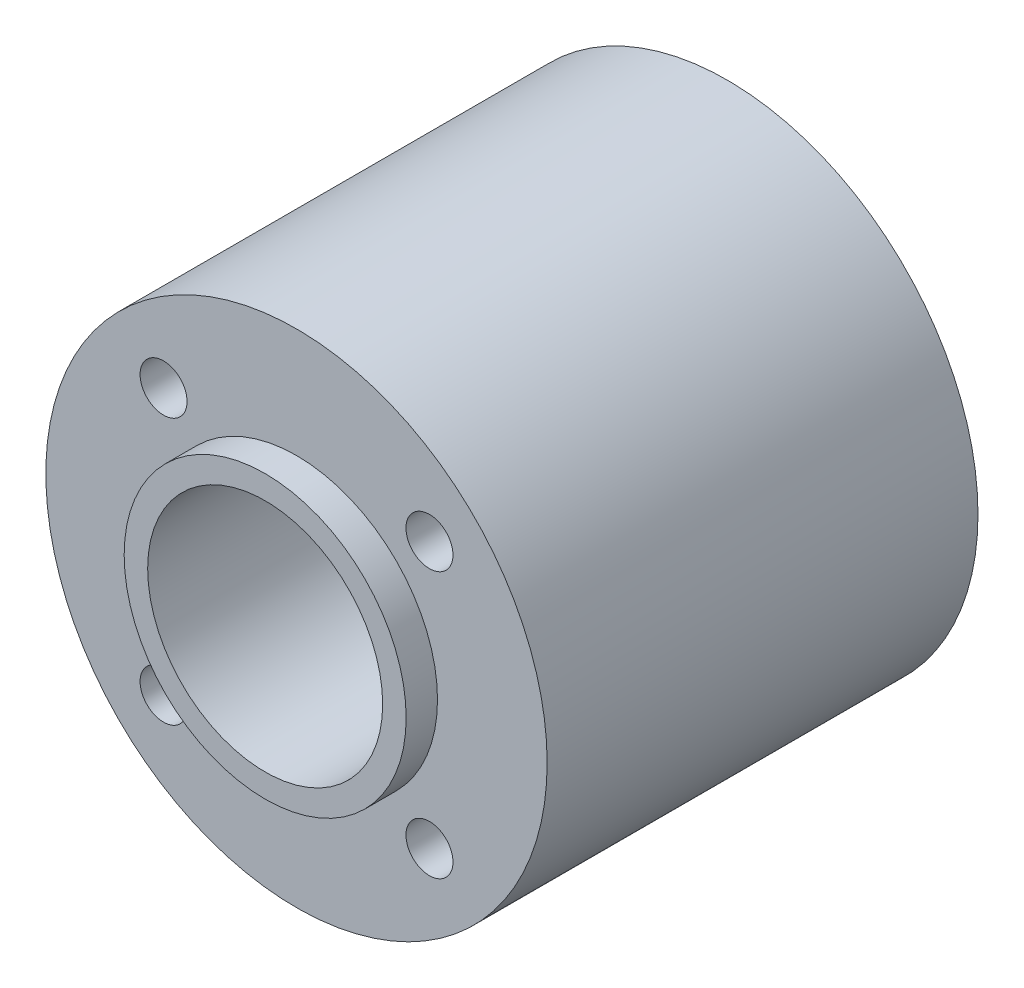
SolidWorks part; units mm, degrees
ref_plane "Front Plane" through (0, 0, 0) normal (0, 0, 1) x (1, 0, 0)
ref_plane "Top Plane" through (0, 0, 0) normal (0, 1, 0) x (1, 0, 0)
ref_plane "Right Plane" through (0, 0, 0) normal (1, 0, 0) x (0, 0, -1)
sketch "Sketch1" plane through (0, 0, 0) normal (0, 0, 1) x (1, 0, 0)
  circle A0 centre (0, 0) radius 9
  circle A1 centre (0, 0) radius 7.5
  circle A2 centre (0, 0) radius 16
  dimension "D1" = 32
  dimension "D2" = 18
  dimension "D3" = 15
extrude "Boss-Extrude1" add sketch "Sketch1" against normal blind 27.5 contours A2 A0 | A0 A1 region at (-8.7454, 0, 0) region at (-15.5475, 0, 0)
extrude "Boss-Extrude2" add sketch "Sketch1<3>" along normal blind 2 contours A0 | A1
sketch "Sketch1<3>" plane through (0, 0, 0) normal (0, 0, 1) x (1, 0, 0) same geometry as "Sketch1"
extrude "Boss-Extrude4" add sketch "Sketch1<5>" against normal blind 2 from surface contours A1 | A0 starting at face at (16, 0, -27.5)
sketch "Sketch1<5>" plane through (0, 0, 0) normal (0, 0, 1) x (1, 0, 0) same geometry as "Sketch1"
sketch "Sketch2" plane through (0, 0, 0) normal (0, 0, 1) x (1, 0, 0)
  line L0 (0, 0) -> (0, 12) construction
  line L1 (0, 12) -> (0, 0) construction
  line L2 (0, 0) -> (-8.4853, 8.4853) construction
  circle A0 centre (0, 0) radius 12 construction
  circle A1 centre (-8.4853, 8.4853) radius 1.5
  circle A2 centre (0.001, -0.001) radius 12.0014 construction
  circle A3 centre (8.4863, 8.4863) radius 1.5
  circle A4 centre (0, 0) radius 12.0014 construction
  circle A5 centre (8.4873, -8.4853) radius 1.5
  circle A6 centre (0.001, -0.001) radius 12 construction
  circle A7 centre (-8.4843, -8.4863) radius 1.5
  circle A10 centre (0, 0) radius 16 construction
  point P21 (0.001, 0)
  dimension "D3" = 3
  dimension "D2" = 45
extrude "Cut-Extrude1" cut sketch "Sketch2" against normal through all
